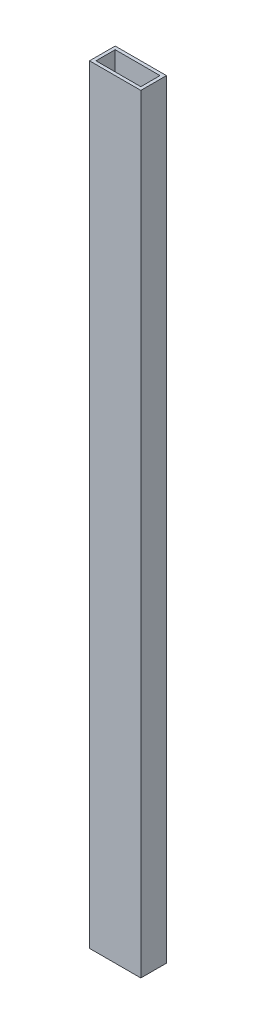
SolidWorks part; units mm, degrees
material "6061 Alloy"
ref_plane "Front Plane" through (0, 0, 0) normal (0, 0, 1) x (1, 0, 0)
ref_plane "Top Plane" through (0, 0, 0) normal (0, 1, 0) x (1, 0, 0)
ref_plane "Right Plane" through (0, 0, 0) normal (1, 0, 0) x (0, 0, -1)
sketch "Sketch1" plane through (0, 0, 0) normal (0, 1, 0) x (1, 0, 0)
  line L0 (-22.225, 9.525) -> (-22.225, 12.7) construction
  line L1 (-25.4, -12.7) -> (25.4, -12.7)
  line L2 (-25.4, -12.7) -> (-25.4, 12.7)
  line L3 (-25.4, 12.7) -> (25.4, 12.7)
  line L4 (25.4, -12.7) -> (25.4, 12.7)
  line L5 (-25.4, -12.7) -> (25.4, 12.7) construction
  line L6 (-25.4, 12.7) -> (25.4, -12.7) construction
  line L7 (-22.225, -9.525) -> (22.225, -9.525)
  line L8 (-22.225, -9.525) -> (-22.225, 9.525)
  line L9 (-22.225, 9.525) -> (22.225, 9.525)
  line L10 (22.225, -9.525) -> (22.225, 9.525)
  line L11 (-22.225, -9.525) -> (22.225, 9.525) construction
  line L12 (-22.225, 9.525) -> (22.225, -9.525) construction
  line L13 (-22.225, 9.525) -> (-25.4, 9.525) construction
  point P0 (0, 0)
  point P6 (0, 0)
  dimension "D1" = 3.175
  dimension "D2" = 50.8
  dimension "D3" = 25.4
extrude "Boss-Extrude1" add sketch "Sketch1" along normal blind 762
sketch "Sketch2" [suppressed] plane through (0, 0, 12.7) normal (0, 0, 1) x (1, 0, 0)
  line L9 (-25.4, 0) -> (-25.4, 12.7)
  line L10 (-25.4, 1219.2) -> (-25.4, 0) construction
  line L11 (-25.4, 12.7) -> (-3.403, 0)
  line L12 (-25.4, 0) -> (25.4, 0) construction
  line L13 (-3.403, 0) -> (-25.4, 0)
  line L14 (25.4, 0) -> (-3.403, 0)
  line L15 (25.4, 0) -> (25.4, 49.8882)
  line L16 (25.4, 1219.2) -> (25.4, 0) construction
  line L17 (25.4, 49.8882) -> (-3.403, 0)
  line L18 (-25.4, 1219.2) -> (25.4, 1219.2) construction
  circle A0 centre (0, 1193.8) radius 19.05
  line M3 (-25.4, 0) -> (25.4, 0)
  line M4 (25.4, 0) -> (25.4, 1219.2)
  line M6 (-25.4, 1219.2) -> (-25.4, 0)
  dimension "D3" = 38.1
  dimension "D1" = 30
  dimension "D2" = 25.4
  dimension "D4" = 38.1
extrude "Cut-Extrude1" [suppressed] cut sketch "Sketch2" against normal through all contours L11 M6 M3 | L17 M4 M3 | A0
